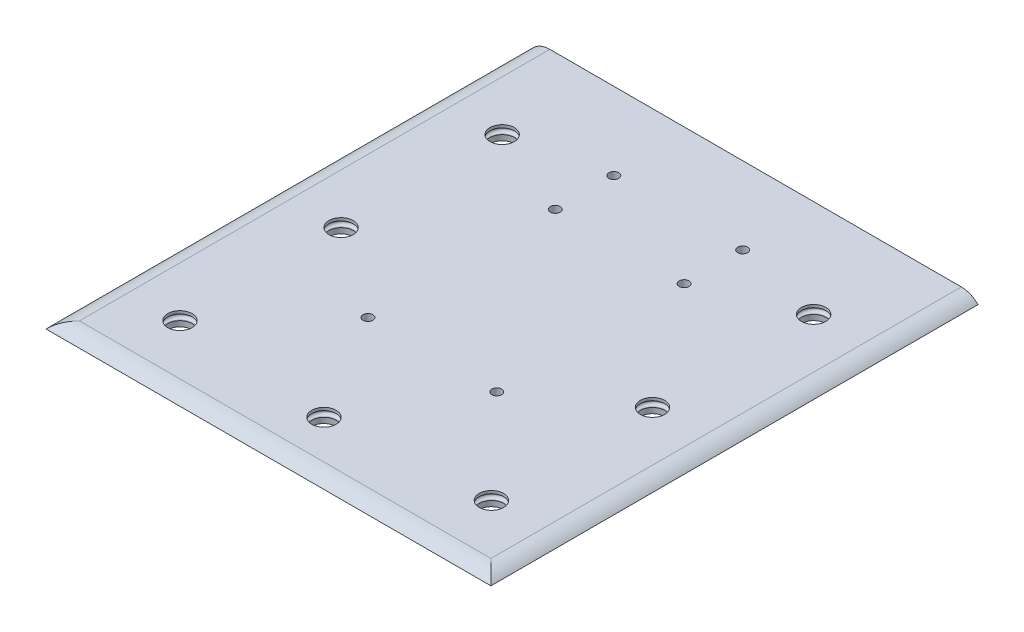
SolidWorks part; units mm, degrees
ref_plane "Спереди" through (0, 0, 0) normal (0, 0, 1) x (1, 0, 0)
ref_plane "Сверху" through (0, 0, 0) normal (0, 1, 0) x (1, 0, 0)
ref_plane "Справа" through (0, 0, 0) normal (1, 0, 0) x (0, 0, -1)
sketch "Эскиз1" plane through (0, 0, 0) normal (0, 1, 0) x (1, 0, 0)
  line L1 (0, 0) -> (190, 0)
  line L2 (0, 0) -> (0, 208)
  line L3 (0, 208) -> (190, 208)
  line L4 (190, 0) -> (190, 208)
  dimension "D1" = 190
  dimension "D2" = 208
extrude "Бобышка-Вытянуть1" add sketch "Эскиз1" along normal blind 3
fillet "Скругление1" radius 10 3 edges at (190, 3, -104) (95, 3, 0) (0, 3, -104)
sketch "Эскиз2" plane through (0, 0, 0) normal (0, -1, 0) x (1, 0, 0)
  line L5 (0, -208) -> (13.5, -208) construction
  line L6 (190, -208) -> (0, -208) construction
  line L7 (176.5, -208) -> (190, -208) construction
  line L8 (13.5, -208) -> (176.5, -208)
  line L9 (13.5, -208) -> (13.5, -8.7)
  line L10 (13.5, -8.7) -> (176.5, -8.7)
  line L11 (176.5, -208) -> (176.5, -8.7)
  dimension "D1" = 163
  dimension "D2" = 199.3
extrude "Бобышка-Вытянуть2" add sketch "Эскиз2" along normal blind 3
sketch "Эскиз3" plane through (0, -3, 0) normal (0, -1, 0) x (1, 0, 0)
  line L0 (54.25, -208) -> (54.25, -86.85) construction
  line L1 (13.5, -208) -> (176.5, -208) construction
  line L3 (135.75, -208) -> (135.75, -86.85) construction
  line L6 (176.5, -8.7) -> (13.5, -8.7) construction
  line L7 (49.25, -208) -> (59.25, -208)
  line L8 (49.25, -208) -> (49.25, -86.85)
  line L9 (49.25, -86.85) -> (59.25, -86.85)
  line L10 (59.25, -208) -> (59.25, -86.85)
  line L11 (49.25, -208) -> (59.25, -86.85) construction
  line L12 (49.25, -86.85) -> (59.25, -208) construction
  line L19 (130.75, -208) -> (140.75, -208)
  line L20 (130.75, -208) -> (130.75, -86.85)
  line L21 (130.75, -86.85) -> (140.75, -86.85)
  line L22 (140.75, -208) -> (140.75, -86.85)
  line L23 (130.75, -208) -> (140.75, -86.85) construction
  line L24 (130.75, -86.85) -> (140.75, -208) construction
  point P14 (54.25, -147.425)
  point P24 (135.75, -147.425)
  dimension "D2" = 10
  dimension "D3" = 78.15
extrude "Бобышка-Вытянуть3" add sketch "Эскиз3" along normal blind 10
sketch "Эскиз4" plane through (0, -3, 0) normal (0, -1, 0) x (1, 0, 0)
  line L20 (49.25, -86.85) -> (49.25, -208) construction
  line L22 (25.5, -208) -> (43.25, -208)
  line L23 (25.5, -208) -> (25.5, -203)
  line L24 (25.5, -203) -> (43.25, -203)
  line L25 (43.25, -208) -> (43.25, -203)
  line L31 (59.25, -208) -> (130.75, -208) construction
  line L32 (86, -208) -> (104, -208)
  line L33 (86, -208) -> (86, -203)
  line L34 (86, -203) -> (104, -203)
  line L35 (104, -208) -> (104, -203)
  line L36 (140.75, -208) -> (176.5, -208) construction
  line L37 (146.75, -208) -> (164.5, -208)
  line L38 (146.75, -208) -> (146.75, -203)
  line L39 (146.75, -203) -> (164.5, -203)
  line L40 (164.5, -208) -> (164.5, -203)
  line L45 (130.75, -86.85) -> (130.75, -208) construction
  line L46 (140.75, -208) -> (140.75, -86.85) construction
  line L48 (176.5, -208) -> (176.5, -8.7) construction
  line L49 (13.5, -8.7) -> (13.5, -208) construction
  dimension "D1" = 6
  dimension "D2" = 5
  dimension "D3" = 18
  dimension "D6" = 26.75
  dimension "D7" = 6
  dimension "D8" = 12
  dimension "D9" = 12
extrude "Бобышка-Вытянуть4" add sketch "Эскиз4" along normal blind 9
sketch "Эскиз5" plane through (0, 0, -208) normal (0, 0, -1) x (-1, 0, 0)
  line L0 (-155.625, -12) -> (-155.625, -8) construction
  line L1 (-146.75, -12) -> (-164.5, -12) construction
  line L2 (-155.625, -8) -> (-4.4957, -8) construction
  line L3 (-34.375, -12) -> (-34.375, -8) construction
  line L4 (-25.5, -12) -> (-43.25, -12) construction
  line L5 (-95, -12) -> (-95, -8) construction
  line L6 (-86, -12) -> (-104, -12) construction
  circle A0 centre (-155.625, -8) radius 2.3
  circle A2 centre (-95, -8) radius 2.3
  circle A3 centre (-34.375, -8) radius 2.3
  dimension "D2" = 4.6
  dimension "D1" = 4
extrude "Вырез-Вытянуть1" cut sketch "Эскиз5" against normal blind 9
sketch "Эскиз6" plane through (140.75, 0, 0) normal (1, 0, 0) x (0, 0, -1)
  line L0 (86.85, -13) -> (86.85, -9) construction
  line L1 (86.85, -13) -> (86.85, -3) construction
  line L2 (86.85, -9) -> (101.85, -9) construction
  circle A0 centre (101.85, -9) radius 2.3
  circle A1 centre (141.85, -9) radius 2.3
  circle A3 centre (181.85, -9) radius 2.3 [skipped]
  dimension "D3" = 4.6
  dimension "D1" = 4
  dimension "D2" = 15
  dimension "D4" = 3
extrude "Вырез-Вытянуть2" cut sketch "Эскиз6" against normal blind 230
sketch "Эскиз7" plane through (0, -3, 0) normal (0, -1, 0) x (1, 0, 0)
  line L0 (95, -8.7) -> (95, -23.7) construction
  line L1 (176.5, -8.7) -> (13.5, -8.7) construction
  line L2 (13.5, -28.7) -> (28.5, -28.7) construction
  line L3 (13.5, -8.7) -> (13.5, -208) construction
  line L4 (13.5, -97.5) -> (28.5, -97.5) construction
  line L5 (13.5, -166.3) -> (28.5, -166.3) construction
  line L6 (13.5, -8.7) -> (13.5, -208) construction
  line L7 (176.5, -28.7) -> (161.5, -28.7) construction
  line L8 (176.5, -208) -> (176.5, -8.7) construction
  line L9 (176.5, -97.5) -> (161.5, -97.5) construction
  line L10 (176.5, -208) -> (176.5, -8.7) construction
  line L11 (176.5, -166.3) -> (161.5, -166.3) construction
  circle A0 centre (95, -23.7) radius 5.2
  circle A1 centre (28.5, -166.3) radius 5.2
  circle A2 centre (28.5, -97.5) radius 5.2
  circle A3 centre (28.5, -28.7) radius 5.2
  circle A4 centre (161.5, -166.3) radius 5.2
  circle A5 centre (161.5, -97.5) radius 5.2
  circle A6 centre (161.5, -28.7) radius 5.2
  dimension "D1" = 10.4
  dimension "D2" = 15
  dimension "D3" = 20
  dimension "D4" = 68.8
  dimension "D5" = 68.8
  dimension "D6" = 20
extrude "Вырез-Вытянуть3" cut sketch "Эскиз7" against normal blind 10
sketch "Эскиз8" plane through (0, 3, 0) normal (0, 1, 0) x (1, 0, 0)
  circle A0 centre (28.5, 166.3) radius 6.7
  circle A1 centre (28.5, 97.5) radius 6.7
  circle A2 centre (28.5, 28.7) radius 6.7
  circle A3 centre (95, 23.7) radius 6.7
  circle A4 centre (161.5, 28.7) radius 6.7
  circle A5 centre (161.5, 97.5) radius 6.7
  circle A6 centre (161.5, 166.3) radius 6.7
  dimension "D1" = 13.4
extrude "Вырез-Вытянуть4" cut sketch "Эскиз8" against normal blind 2.5 from offset 1.2 offset against normal yes
fillet "Скругление2" radius 1.2 14 edges at (161.5, -0.7, -90.8) (161.5, -0.7, -22) (95, -0.7, -17) (28.5, -0.7, -22) (28.5, -0.7, -90.8) (28.5, -0.7, -159.6) (161.5, -0.7, -159.6) (28.5, 1.8, -90.8) (28.5, 1.8, -159.6) (161.5, 1.8, -159.6) (161.5, 1.8, -90.8) (161.5, 1.8, -22) (95, 1.8, -17) (28.5, 1.8, -22)
sketch "Эскиз9" plane through (0, 0, 0) normal (0, -1, 0) x (1, 0, 0)
  line L0 (13.5, -208) -> (9.5, -208) construction
  line L1 (13.5, -208) -> (0, -208) construction
  line L2 (176.5, -208) -> (180.5, -208) construction
  line L3 (190, -208) -> (176.5, -208) construction
  line L4 (95, -8.7) -> (95, -4.7) construction
  line L5 (176.5, -8.7) -> (13.5, -8.7) construction
  line L6 (9.5, -208) -> (9.5, -10.7)
  line L7 (15.5, -4.7) -> (174.5, -4.7)
  line L8 (180.5, -10.7) -> (180.5, -208)
  arc A0 (174.5, -4.7) -> (180.5, -10.7) centre (174.5, -10.7) cw
  arc A1 (9.5, -10.7) -> (15.5, -4.7) centre (15.5, -10.7) cw
  dimension "D2" = 6
  dimension "D1" = 4
sketch "Эскиз10" plane through (0, 0, -208) normal (0, 0, -1) x (-1, 0, 0)
  line L0 (-9.5, 0) -> (-9.5, -0.15) construction
  line L1 (-15.5, 0) -> (-174.5, 0) construction
  line L2 (0, 0) -> (-190, 0) construction
  circle A0 centre (-9.5, -0.15) radius 1.35
  dimension "D1" = 2.7
  dimension "D2" = 0.15
sweep "Вырез-По траектории1" [suppressed] cut profiles "Эскиз10" path "Эскиз9"
sketch "Эскиз11" plane through (0, 3, 0) normal (0, 1, 0) x (1, 0, 0)
  line L0 (95, 0) -> (95, 70) construction
  line L1 (0, 0) -> (190, 0) construction
  line L2 (95, 70) -> (95, 150) construction
  line L3 (95, 150) -> (95, 175) construction
  line L4 (67.5, 70) -> (122.5, 70) construction
  line L5 (67.5, 150) -> (122.5, 150) construction
  line L6 (67.5, 175) -> (122.5, 175) construction
  circle A0 centre (67.5, 70) radius 2.1
  circle A1 centre (122.5, 70) radius 2.1
  circle A2 centre (122.5, 150) radius 2.1
  circle A3 centre (122.5, 175) radius 2.1
  circle A4 centre (67.5, 175) radius 2.1
  circle A5 centre (67.5, 150) radius 2.1
  point P9 (95, 70)
  point P12 (95, 150)
  point P15 (95, 175)
  dimension "D2" = 4.2
  dimension "D1" = 55
  dimension "D3" = 70
  dimension "D4" = 80
  dimension "D5" = 25
extrude "Вырез-Вытянуть5" cut sketch "Эскиз11" against normal blind 5
